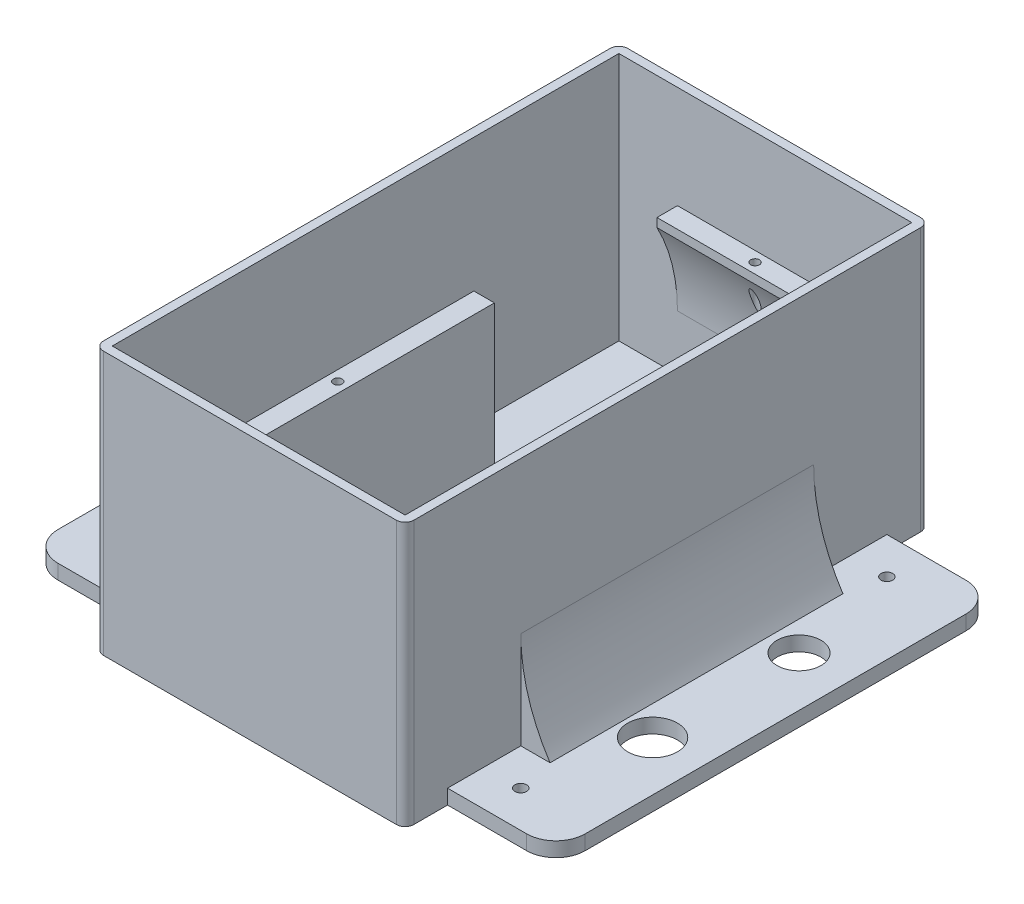
SolidWorks part; units mm, degrees
ref_plane "Alzado" through (0, 0, 0) normal (0, 0, 1) x (1, 0, 0)
ref_plane "Planta" through (0, 0, 0) normal (0, 1, 0) x (1, 0, 0)
ref_plane "Vista lateral" through (0, 0, 0) normal (1, 0, 0) x (0, 0, -1)
sketch "Croquis1" plane through (0, 0, 0) normal (0, 1, 0) x (1, 0, 0)
  line L1 (-50, 86.5) -> (50, 86.5)
  line L2 (-50, 86.5) -> (-50, -86.5)
  line L3 (-50, -86.5) -> (50, -86.5)
  line L4 (50, 86.5) -> (50, -86.5)
  line L5 (-39.5, 26.5) -> (-32.5, 26.5)
  line L6 (0, -86.5) -> (0, 86.5) construction
  line L7 (39.5, 26.5) -> (39.5, -75.5)
  line L8 (-32.5, -73.5) -> (32.5, -73.5)
  line L9 (-32.5, -73.5) -> (-32.5, 26.5)
  line L11 (32.5, -73.5) -> (32.5, 26.5)
  line L12 (-32.5, -73.5) -> (32.5, 26.5) construction
  line L13 (-32.5, 26.5) -> (32.5, -73.5) construction
  line L14 (39.5, -75.5) -> (0, -75.5)
  line L15 (-39.5, -73.5) -> (-39.5, 26.5)
  line L16 (0, -75.5) -> (0, -73.5)
  line L17 (-32.5, -73.5) -> (-39.5, -73.5)
  line L18 (-39.5, 26.5) -> (-32.5, 26.5)
  line L19 (32.5, 26.5) -> (39.5, 26.5)
  line L21 (-53, -89.5) -> (53, -89.5)
  line L22 (-53, -89.5) -> (-53, 89.5)
  line L23 (-53, 89.5) -> (53, 89.5)
  line L24 (53, -89.5) -> (53, 89.5)
  line L25 (-53, -89.5) -> (53, 89.5) construction
  line L26 (-53, 89.5) -> (53, -89.5) construction
  circle A0 centre (-36, -23.5) radius 1.5
  circle A1 centre (36, -23.5) radius 1.5
  point P0 (0, 0)
  point P12 (0, -23.5)
  point P20 (0, 0)
  dimension "D11" = 3
  dimension "D12" = 3.5
  dimension "D1" = 100
  dimension "D2" = 3
  dimension "D3" = 3
  dimension "D4" = 60
  dimension "D5" = 100
  dimension "D6" = 7
  dimension "D7" = 7
  dimension "D8" = 2
  dimension "D9" = 11
  dimension "D10" = 65
extrude "Saliente-Extruir7" add sketch "Croquis1" along normal blind 3 contours L17 L9 L5 L15 | L16 L14 L7 L5 L11 L8 | L2 L5 L4 region at (-0.0986, 0, -2.4515) region at (34.337, 0, 28.7194) region at (-36, 0, -25.4976)
extrude "Saliente-Extruir8" add sketch "Croquis1<13>" along normal blind 5 contours L2 L3 L4 L1
sketch "Croquis1<13>" plane through (0, 0, 0) normal (0, 1, 0) x (1, 0, 0) same geometry as "Croquis1"
extrude "Saliente-Extruir9" add sketch "Croquis1<16>" along normal blind 90 contours L21 L24 L23 L22 L1 L4 L3 L2 region at (-50.9197, 0, 0)
sketch "Croquis1<16>" plane through (0, 0, 0) normal (0, 1, 0) x (1, 0, 0) same geometry as "Croquis1"
fillet "Redondeo1" radius 3 4 edges at (53, 45, -89.5) (-53, 45, -89.5) (-53, 45, 89.5) (53, 45, 89.5)
sketch "Croquis4" plane through (0, 0, 0) normal (0, 1, 0) x (1, 0, 0)
  line L0 (0, 0) -> (-53, 0) construction
  line L1 (-53, -75) -> (-90, -75)
  line L2 (-53, -75) -> (-53, 75)
  line L3 (-53, 75) -> (-90, 75)
  line L4 (-90, -75) -> (-90, 75)
  line L5 (-53, -89.5) -> (-53, 89.5) construction
  line L6 (0, 0) -> (0, 89.5) construction
  line L7 (-53, 89.5) -> (53, 89.5) construction
  line L8 (53, 75) -> (90, 75)
  line L9 (90, -75) -> (90, 75)
  line L10 (53, -75) -> (90, -75)
  line L11 (53, -75) -> (53, 75)
  circle A0 centre (73, 25) radius 7.5
  circle A1 centre (73, -25) radius 8.5
  point P10 (-53, 0)
  dimension "D3" = 50
  dimension "D6" = 15
  dimension "D7" = 17
  dimension "D8" = 20
  dimension "D10" = 20
  dimension "D1" = 37
  dimension "D2" = 150
  dimension "D4" = 50
  dimension "D5" = 50
  dimension "D9" = 37
extrude "Saliente-Extruir10" add sketch "Croquis4" along normal blind 5
sketch "Croquis5" plane through (0, 0, 0) normal (0, 0, 1) x (1, 0, 0)
  line L0 (-53, 5) -> (-53, 20) construction
  line L4 (-53, 5) -> (-53, 20)
  line L7 (53, 5) -> (53, 20)
  line L8 (-53, 5) -> (-63, 5)
  line L12 (-90, 5) -> (-53, 5) construction
  line L13 (-63, 5) -> (-53, 20)
  line L14 (53, 5) -> (63, 5)
  line L15 (53, 5) -> (90, 5) construction
  line L16 (63, 5) -> (53, 20)
  dimension "D1" = 15
  dimension "D2" = 10
  dimension "D3" = 15
  dimension "D4" = 10
extrude "Saliente-Extruir11" add sketch "Croquis5" along normal blind 50 and the other way blind 50
fillet "Redondeo2" radius 10 4 edges at (-90, 2.5, 75) (-90, 2.5, -75) (90, 2.5, 75) (90, 2.5, -75)
extrude "Saliente-Extruir12" add sketch "Croquis1<17>" along normal blind 55 contours L17 L9 L5 L15 | L19 L11 L8 L16 L14 L7 region at (34.337, 0, 28.7194) region at (-36, 0, -25.4976)
sketch "Croquis1<17>" plane through (0, 0, 0) normal (0, 1, 0) x (1, 0, 0) same geometry as "Croquis1"
ref_plane "Plano1" through (0, 70, 0) normal (0, 1, 0) x (1, 0, 0)
sketch "Croquis12" plane through (0, 0, -86.5) normal (0, 0, 1) x (1, 0, 0)
  line L0 (0, 0) -> (0, 70) construction
  line L1 (55, 70) -> (-55, 70) construction
  line L2 (-50, 5) -> (50, 5) construction
  line L3 (-30, 55) -> (30, 55)
  line L4 (-30, 55) -> (-30, 52)
  line L5 (-30, 52) -> (30, 52)
  line L6 (30, 55) -> (30, 52)
  line L7 (-30, 55) -> (30, 52) construction
  line L8 (-30, 52) -> (30, 55) construction
  point P5 (0, 53.5)
  dimension "D1" = 60
  dimension "D2" = 3
  dimension "D3" = 47
extrude "Saliente-Extruir13" add sketch "Croquis12" along normal blind 7
sketch "Croquis16" plane through (0, 55, 0) normal (0, 1, 0) x (1, 0, 0)
  line L0 (30, 79.5) -> (-30, 79.5) construction
  circle A0 centre (0, 83) radius 1.5
  dimension "D1" = 3
  dimension "D2" = 3.5
extrude "Cortar-Extruir5" cut sketch "Croquis16" against normal blind 10
sketch "Croquis17" plane through (0, 5, 0) normal (0, 1, 0) x (1, 0, 0)
  line L0 (80, 75) -> (53, 75) construction
  line L1 (53, 75) -> (53, 50) construction
  line L2 (53, -75) -> (80, -75) construction
  line L3 (53, -50) -> (53, -75) construction
  line L4 (-80, -75) -> (-53, -75) construction
  line L5 (-53, -75) -> (-53, -50) construction
  line L6 (-53, 50) -> (-53, 75) construction
  line L7 (-53, 75) -> (-80, 75) construction
  circle A0 centre (-65.5, 62.5) radius 2
  circle A1 centre (65.5, 62.5) radius 2
  circle A2 centre (65.5, -62.5) radius 2
  circle A3 centre (-65.5, -62.5) radius 2
  dimension "D1" = 4
  dimension "D2" = 4
  dimension "D3" = 4
  dimension "D4" = 4
  dimension "D5" = 12.5
  dimension "D9" = 12.5
  dimension "D10" = 12.5
  dimension "D11" = 12.5
  dimension "D12" = 12.5
  dimension "D6" = 12.5
  dimension "D7" = 12.5
  dimension "D8" = 12.5
extrude "Cortar-Extruir6" cut sketch "Croquis17" against normal blind 10
sketch "Croquis19" plane through (0, 5, 0) normal (0, 1, 0) x (1, 0, 0)
  line L0 (-53, 75) -> (-80, 75) construction
  line L2 (-53, 50) -> (-53, 75) construction
  line L5 (-53, -86.5) -> (-53, 86.5) construction
  circle A0 centre (-73, 25) radius 3.5
  circle A2 centre (-71.5, -25) radius 5
  dimension "D4" = 50
  dimension "D5" = 7
  dimension "D6" = 20
  dimension "D2" = 18.5
  dimension "D3" = 10
  dimension "D1" = 50
extrude "Cortar-Extruir7" cut sketch "Croquis19" against normal blind 10
fillet "Redondeo3" radius 60 2 edges at (53, 20, 0) (-53, 20, 0)
fillet "Redondeo4" radius 60 1 edges at (0, 52, -86.5)
